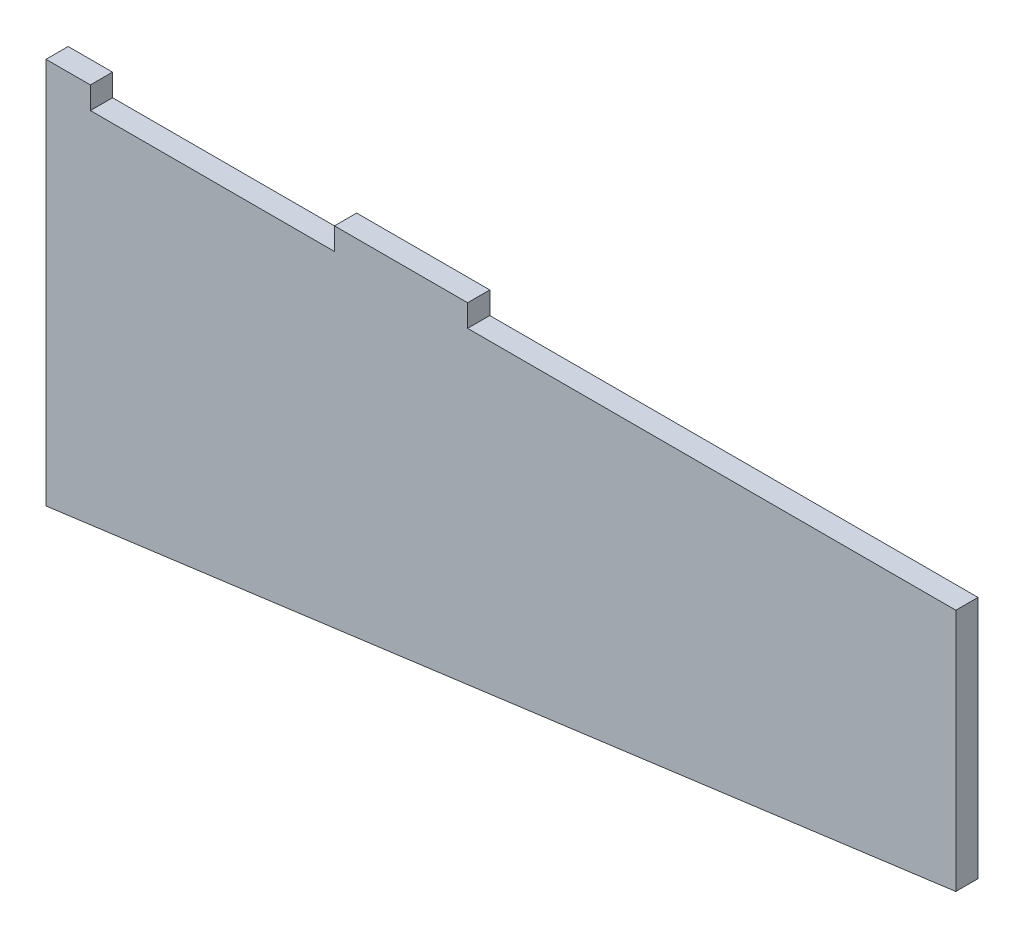
SolidWorks part; units mm, degrees
ref_plane "Front Plane" through (0, 0, 0) normal (0, 0, 1) x (1, 0, 0)
ref_plane "Top Plane" through (0, 0, 0) normal (0, 1, 0) x (1, 0, 0)
ref_plane "Right Plane" through (0, 0, 0) normal (1, 0, 0) x (0, 0, -1)
sketch "Sketch1" plane through (0, 0, 0) normal (0, 0, 1) x (1, 0, 0)
  line L0 (0, 0) -> (12.7, 0)
  line L4 (12.7, 0) -> (12.7, -6.35)
  line L5 (12.7, -6.35) -> (82.55, -6.35)
  line L6 (82.55, -6.35) -> (82.55, 0)
  line L7 (82.55, 0) -> (120.65, 0)
  line L8 (120.65, 0) -> (120.65, -6.35)
  line L9 (120.65, -6.35) -> (203.2, -6.35)
  line L12 (0, -110.6942) -> (0, 0)
  line L13 (203.2, -6.35) -> (260.35, -6.35)
  line L14 (260.35, -6.35) -> (260.35, -76.0643)
  line L15 (0, -110.6942) -> (260.35, -76.0643)
  line L16 (260.35, 127) -> (260.35, 58.8285) construction
  dimension "D1" = 12.7
  dimension "D2" = 6.35
  dimension "D3" = 69.85
  dimension "D4" = 38.1
  dimension "D5" = 82.55
  dimension "D6" = 57.15
extrude "Boss-Extrude1" add sketch "Sketch1" along normal blind 6.35
